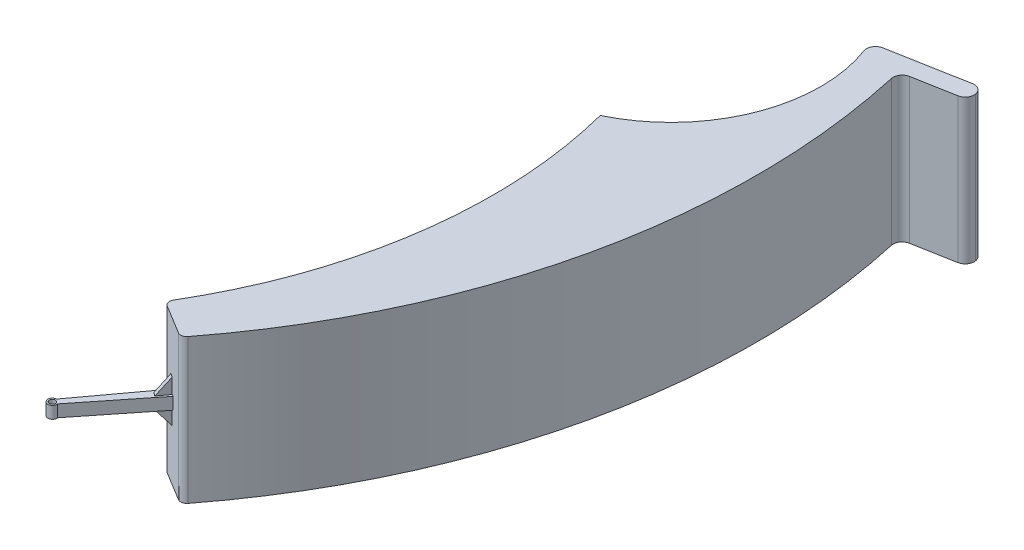
SolidWorks part; units mm, degrees
ref_plane "Front Plane" through (0, 0, 0) normal (0, 0, 1) x (1, 0, 0)
ref_plane "Top Plane" through (0, 0, 0) normal (0, 1, 0) x (1, 0, 0)
ref_plane "Right Plane" through (0, 0, 0) normal (1, 0, 0) x (0, 0, -1)
sketch "Sketch5" plane through (0, 0, 0) normal (0, 1, 0) x (1, 0, 0)
  line L0 (16.6797, -62.5885) -> (23.0829, -66.4936)
  line L1 (37.984, 33.1013) -> (53.8841, 36.011)
  line L2 (53.8841, 36.011) -> (54.4242, 33.06)
  line L3 (54.4242, 33.06) -> (44.5875, 31.2599)
  arc A2 (26.0818, 0.2533) -> (37.984, 33.1013) centre (15.2969, 22.7415) ccw
  arc A3 (26.0818, 0.2533) -> (16.6797, -62.5885) centre (-53.1156, -20.0218) cw
  arc A4 (44.5875, 31.2599) -> (23.0829, -66.4936) centre (-67.7103, 4.722) cw
  dimension "D2" = 7.5
  dimension "D4" = 3
  dimension "D5" = 10
extrude "Boss-Extrude4" add sketch "Sketch5" along normal blind 24
shell "Shell1" thickness 2 removed face at (24.5584, 12, 31.643)
sketch "Sketch9" plane through (0, 22, 0) normal (0, -1, 0) x (-1, 0, 0)
  line L0 (-18.8025, -7.0442) -> (-31.2835, -4.6602)
  line L2 (-44.9027, 14.3733) -> (-42.8099, 29.9242)
  line L3 (-42.8099, 29.9242) -> (-24.7981, 26.4838)
  line L4 (-24.7981, 26.4838) -> (-18.8025, -7.0442)
  line L5 (-33, 1.7896) -> (-36.8538, 0.8789)
  line L6 (-36.8538, 0.8789) -> (-41.7044, 7.2079)
  line L7 (-41.7044, 7.2079) -> (-44.9027, 14.3733)
  line L8 (-33, 1.7896) -> (-31.2835, 0.8789)
  line L9 (-31.2835, 0.8789) -> (-31.2835, -4.6602)
  circle A0 centre (-33, 0) radius 1
  dimension "D1" = 2
  dimension "D2" = 33
extrude "Cut-Extrude1" cut sketch "Sketch9" along normal blind 22
sketch "Sketch6" plane through (0, 24, 0) normal (0, 1, 0) x (1, 0, 0)
  circle A0 centre (33, 0) radius 1
  dimension "D2" = 2
  dimension "D1" = 33
extrude "Boss-Extrude5" add sketch "Sketch6" against normal blind 4
sketch "Sketch8" plane through (0, 0, 0) normal (0, -1, 0) x (-1, 0, 0)
  circle A0 centre (-33, 0) radius 1
  dimension "D2" = 2
  dimension "D1" = 33
extrude "Boss-Extrude6" add sketch "Sketch8" against normal blind 4
sketch "Sketch11" plane through (0, 24, 0) normal (0, 1, 0) x (1, 0, 0)
  line L0 (16.6797, -62.5885) -> (23.0829, -66.4936)
  line L1 (18.5476, -63.7276) -> (28.9612, -46.6526) construction
  line L2 (24.9452, -44.308) -> (34.0742, -49.6377)
  arc A0 (16.6797, -62.5885) -> (26.0818, 0.2533) centre (-53.1156, -20.0218) ccw construction
  arc A1 (23.0829, -66.4936) -> (44.5875, 31.2599) centre (-67.7103, 4.722) ccw construction
  arc A2 (24.9452, -44.308) -> (16.6797, -62.5885) centre (-53.1156, -20.0218) cw
  arc A3 (34.0742, -49.6377) -> (23.0829, -66.4936) centre (-67.7103, 4.722) cw
  dimension "D1" = 20
extrude "Boss-Extrude7" add sketch "Sketch11" against normal blind 24
sketch "Sketch10" plane through (-23.3006, 0, 38.2053) normal (-0.5207, 0, 0.8537) x (0.8537, 0, 0.5207)
  line L1 (48.0791, 17) -> (53.0791, 17)
  line L2 (48.0791, 17) -> (48.0791, 7)
  line L3 (48.0791, 7) -> (53.0791, 7)
  line L4 (53.0791, 17) -> (53.0791, 7)
  line L5 (46.8291, 0) -> (54.3291, 0) construction
  line L6 (54.3291, 24) -> (54.3291, 0) construction
  dimension "D1" = 5
  dimension "D2" = 10
  dimension "D3" = 7
  dimension "D4" = 1.25
extrude "Cut-Extrude2" [suppressed] cut sketch "Sketch10" against normal blind 15
fillet "Fillet1" radius 1 2 edges at (16.6797, 12, 62.5885) (23.0829, 12, 66.4936)
fillet "Fillet2" radius 1.5 5 edges at (39.3687, 11, -29.2669) (37.984, 12, -33.1013) (53.8841, 12, -36.011) (54.4242, 12, -33.06) (44.5875, 12, -31.2599)
fillet "Fillet3" [suppressed] radius 1.5
sketch "Sketch12" plane through (0, 0, 0) normal (0, 1, 0) x (1, 0, 0)
  line L0 (18.7156, -63.8301) -> (10.7281, -74.6644)
  line L1 (17.5283, -63.106) -> (22.321, -66.029) construction
  line L3 (11.5045, -75.2823) -> (19.9962, -64.6111)
  line L4 (19.9962, -64.6111) -> (18.7156, -63.8301)
  arc A1 (10.7281, -74.6644) -> (11.5045, -75.2823) centre (10.7661, -75.4135) ccw
  circle A2 centre (10.7661, -75.4135) radius 0.5
  dimension "D2" = 1
  dimension "D3" = 1.5
  dimension "D1" = 1.5
extrude "Boss-Extrude8" add sketch "Sketch12" along normal blind 24
sketch "Sketch13" plane through (0, 0, 0) normal (0, 1, 0) x (1, 0, 0)
  line L0 (19.9962, -64.6111) -> (24.8855, -67.593)
  line L1 (24.8855, -67.593) -> (14.4821, -80.6703)
  line L2 (14.4821, -80.6703) -> (6.5514, -74.3612)
  line L3 (6.5514, -74.3612) -> (17.5283, -63.106)
  line L4 (17.5283, -63.106) -> (19.9962, -64.6111)
extrude "Cut-Extrude3" cut sketch "Sketch13" along normal blind 11
sketch "Sketch14" plane through (0, 24, 0) normal (0, 1, 0) x (1, 0, 0)
  line L0 (19.9962, -64.6111) -> (15.9183, -82.2974)
  line L1 (15.9183, -82.2974) -> (4.93, -72.5052)
  line L2 (4.93, -72.5052) -> (18.705, -63.8236)
  line L3 (17.5283, -63.106) -> (18.7156, -63.8301) construction
  line L4 (18.705, -63.8236) -> (19.9962, -64.6111)
extrude "Cut-Extrude4" cut sketch "Sketch14" against normal blind 11
sketch "Sketch15" plane through (0, 13, 0) normal (0, 1, 0) x (1, 0, 0)
  line L0 (19.0188, -64.015) -> (17.8405, -65.6537)
  line L1 (19.9962, -64.6111) -> (18.7156, -63.8301) construction
  line L2 (17.8405, -65.6537) -> (18.4477, -66.0903)
  line L3 (18.4477, -66.0903) -> (19.6591, -64.4055)
  line L4 (17.5283, -63.106) -> (22.321, -66.029) construction
  line L5 (19.6591, -64.4055) -> (19.0188, -64.015)
  dimension "D1" = 0.75
extrude "Boss-Extrude9" add sketch "Sketch15" along normal blind 2.5 and the other way blind 4.5
sketch "Sketch16" plane through (43.4861, 0, 31.2679) normal (0.8119, 0, 0.5838) x (0.5838, 0, -0.8119)
  line L0 (-42.8896, 13) -> (-40.8146, 15.5)
  line L1 (-40.8146, 15.5) -> (-42.8896, 15.5)
  line L2 (-42.8896, 15.5) -> (-42.8896, 13)
  line L3 (-42.8896, 11) -> (-40.8146, 8.5)
  line L4 (-40.8146, 8.5) -> (-42.8896, 8.5)
  line L5 (-42.8896, 8.5) -> (-42.8896, 11)
extrude "Cut-Extrude5" cut sketch "Sketch16" against normal up to surface (0.7479 mm away) up to face at (18.4297, 14.25, 64.8344)
